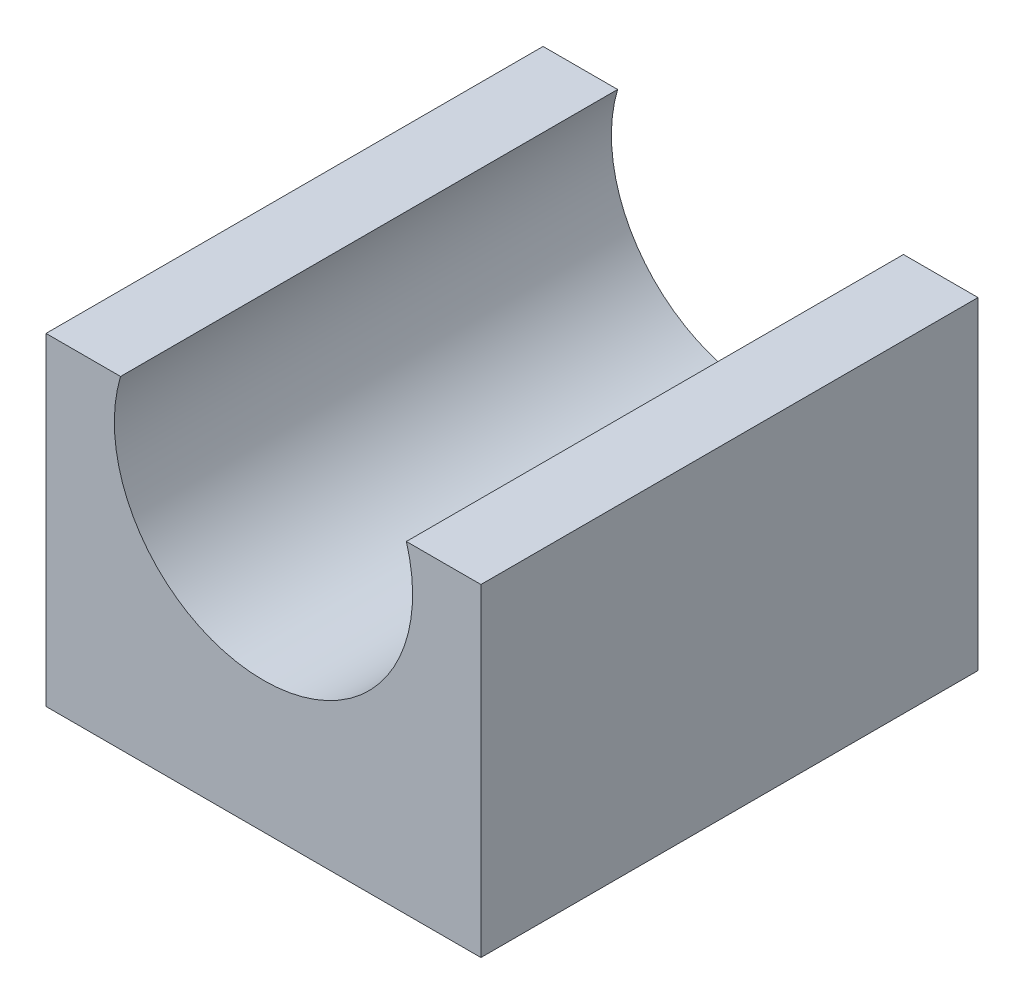
SolidWorks part; units mm, degrees
ref_plane "Front Plane" through (0, 0, 0) normal (0, 0, 1) x (1, 0, 0)
ref_plane "Top Plane" through (0, 0, 0) normal (0, 1, 0) x (1, 0, 0)
ref_plane "Right Plane" through (0, 0, 0) normal (1, 0, 0) x (0, 0, -1)
sketch "Sketch1" plane through (0, 0, 0) normal (0, 0, 1) x (1, 0, 0)
  line L0 (-5.75, 6.5) -> (-8.75, 6.5)
  line L1 (8.75, -6.5) -> (-8.75, -6.5)
  line L2 (8.75, -6.5) -> (8.75, 6.5)
  line L3 (8.75, 6.5) -> (5.75, 6.5)
  line L4 (-8.75, -6.5) -> (-8.75, 6.5)
  line L5 (8.75, -6.5) -> (-8.75, 6.5) construction
  line L6 (8.75, 6.5) -> (-8.75, -6.5) construction
  arc A0 (-5.75, 6.5) -> (5.75, 6.5) centre (0, 4.7861) ccw
  point P0 (0, 0)
  point P7 (-5.75, 6.2224)
  dimension "D1" = 12
  dimension "D2" = 3
  dimension "D3" = 17.5
  dimension "D4" = 13
extrude "Boss-Extrude1" add sketch "Sketch1" along normal blind 20
